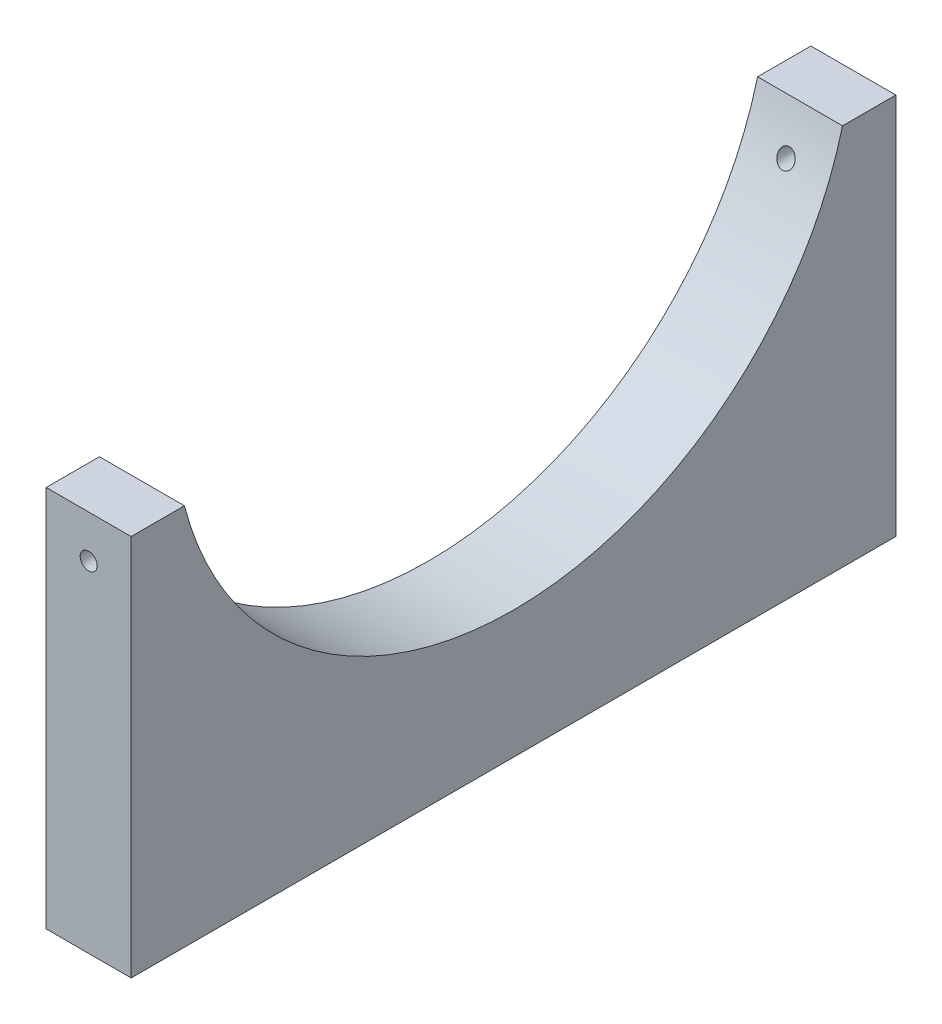
SolidWorks part; units mm, degrees
material "1060 Alloy"
ref_plane "Front Plane" through (0, 0, 0) normal (0, 0, 1) x (1, 0, 0)
ref_plane "Top Plane" through (0, 0, 0) normal (0, 1, 0) x (1, 0, 0)
ref_plane "Right Plane" through (0, 0, 0) normal (1, 0, 0) x (0, 0, -1)
sketch "Sketch1" plane through (0, 0, 0) normal (0, 1, 0) x (1, 0, 0)
  line L1 (-68.4091, -36.25) -> (121.0909, -36.25)
  line L2 (-68.4091, -36.25) -> (-68.4091, 53.75)
  line L3 (-68.4091, 53.75) -> (121.0909, 53.75)
  line L4 (121.0909, -36.25) -> (121.0909, 53.75)
  dimension "D1" = 90
  dimension "D2" = 189.5
extrude "Boss-Extrude1" add sketch "Sketch1" along normal blind 80
sketch "Sketch3" plane through (0, 0, 36.25) normal (0, 0, 1) x (1, 0, 0)
  line L0 (-68.4091, 0) -> (121.0909, 0) construction
  line L1 (-68.4091, 80) -> (-68.4091, 0) construction
  circle A0 centre (-6.7091, 45) radius 8.15
  circle A1 centre (44.2909, 45) radius 8.15
  circle A2 centre (95.2909, 45) radius 8.15
  dimension "D1" = 16.3
  dimension "D2" = 16.3
  dimension "D3" = 16.3
  dimension "D5" = 0
  dimension "D7" = 51
  dimension "D8" = 51
  dimension "D9" = 61.7
  dimension "D4" = 45
  dimension "D6" = 0
extrude "Cut-Extrude2" cut sketch "Sketch3" against normal blind 40
sketch "Sketch4" plane through (0, 0, -53.75) normal (0, 0, -1) x (-1, 0, 0)
  line L0 (68.4091, 0) -> (-121.0909, 0) construction
  circle A0 centre (-18.7909, 45) radius 10.3
  circle A1 centre (-44.2909, 45) radius 8.15 construction
  dimension "D1" = 20.6
  dimension "D2" = 25.5
  dimension "D3" = 45
extrude "Cut-Extrude3" cut sketch "Sketch4" against normal blind 40
sketch "Sketch2" plane through (-68.4091, 0, 0) normal (-1, 0, 0) x (0, 0, 1)
  line L0 (36.25, 80) -> (36.25, 0) construction
  line L1 (-53.75, 0) -> (36.25, 0) construction
  line L2 (-90.6382, 55) -> (87.3005, 55)
  line L3 (-48.75, 55) -> (31.25, 55)
  line L4 (-48.75, 55) -> (-48.75, 118.783)
  line L5 (-48.75, 118.783) -> (31.25, 118.783)
  line L6 (31.25, 55) -> (31.25, 118.783)
  line L7 (-80.7671, 45) -> (67.381, 45)
  circle A0 centre (-8.75, 55) radius 40
  line M2 (36.25, 0) -> (36.25, 80)
  line M3 (36.25, 80) -> (-53.75, 80)
  line M4 (-53.75, 80) -> (-53.75, 0)
  dimension "D1" = 80
  dimension "D2" = 45
  dimension "D3" = 55
  dimension "D4" = 80
  dimension "D5" = 10
extrude "Cut-Extrude1" cut sketch "Sketch2" against normal through all contours A0 L2 L7 M4 | L2 A0 L7 | L7 A0 | A0 L7 L2 M2 | L6 L2 M2 M3 | A0 L6 M3 | L2 A0 M3 | A0 L4 M3 | L2 L4 M3 M4 region at (-68.4091, 67.0217, -8.75) region at (-68.4091, 49.8054, -51.0265) region at (-68.4091, 67.5, -51.25) region at (-68.4091, 73.8954, -46.1757) region at (-68.4091, 50.0267, -8.75) region at (-68.4091, 67.5, 33.75) region at (-68.4091, 73.8954, 28.6757) region at (-68.4091, 49.8054, 33.5265) region at (-68.4091, 32.5047, -8.75)
sketch "Sketch5" plane through (-68.4091, 0, 0) normal (-1, 0, 0) x (0, 0, 1)
  circle A0 centre (-14.4166, 36.2789) radius 83.6376
extrude "Cut-Extrude5" cut sketch "Sketch5" against normal through all from offset 10 offset against normal yes
sketch "Sketch6" plane through (0, 0, 0) normal (0, -1, 0) x (1, 0, 0)
  line L0 (-58.4091, 36.25) -> (-58.4091, -53.75) construction
  line L1 (-68.4091, 36.25) -> (-58.4091, 36.25) construction
  line L2 (-58.4091, -53.75) -> (-68.4091, -53.75) construction
  circle A0 centre (-63.4091, 21.25) radius 2
  circle A1 centre (-63.4091, -38.75) radius 2
  dimension "D1" = 4
  dimension "D2" = 4
  dimension "D6" = 15
  dimension "D3" = 5
  dimension "D4" = 5
  dimension "D5" = 15
extrude "Cut-Extrude6" cut sketch "Sketch6" against normal blind 15
sketch "Sketch7" plane through (0, 0, 36.25) normal (0, 0, 1) x (1, 0, 0)
  line L0 (-58.4091, 0) -> (-58.4091, 45) construction
  line L4 (-58.4091, 45) -> (-68.4091, 45) construction
  circle A0 centre (-63.4091, 40) radius 1
  dimension "D1" = 2
  dimension "D2" = 5
  dimension "D3" = 5
extrude "Cut-Extrude7" cut sketch "Sketch7" against normal through all both and the other way through all
